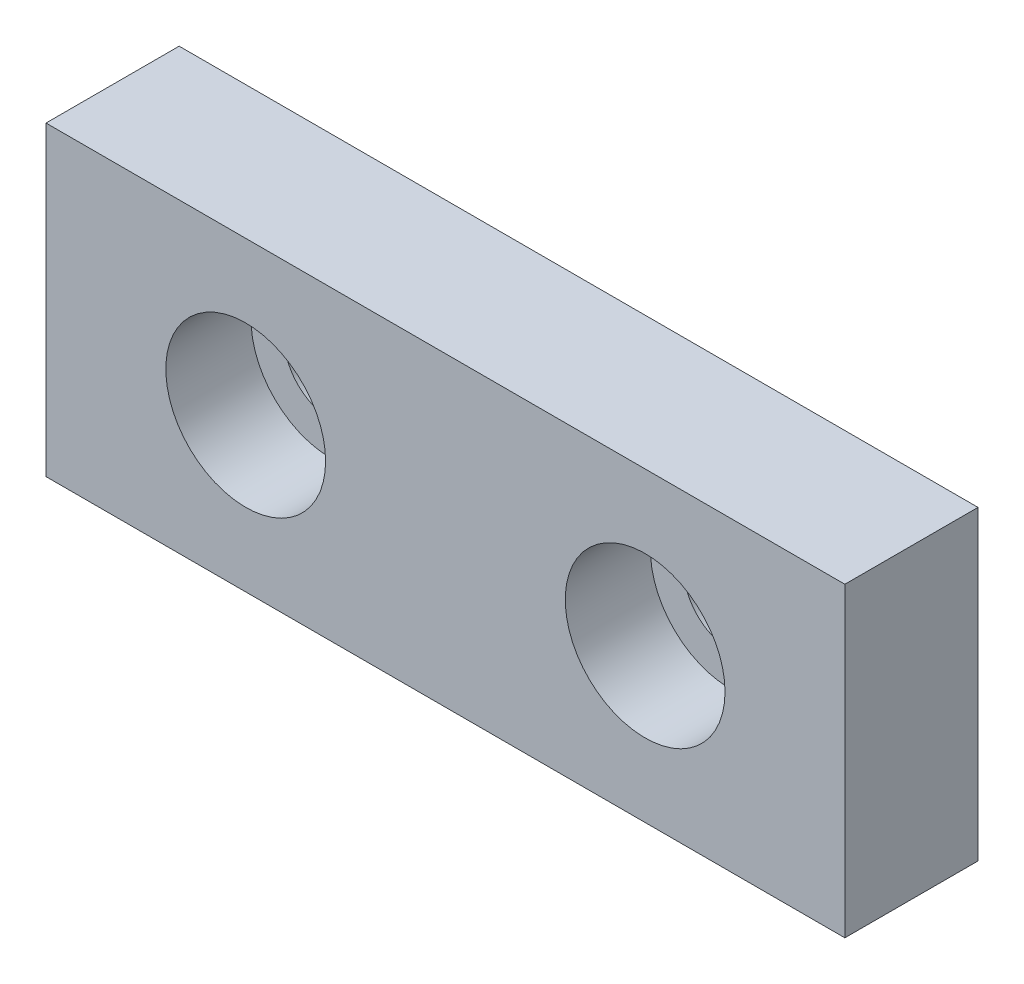
SolidWorks part; units mm, degrees
ref_plane "Front Plane" through (0, 0, 0) normal (0, 0, 1) x (1, 0, 0)
ref_plane "Top Plane" through (0, 0, 0) normal (0, 1, 0) x (1, 0, 0)
ref_plane "Right Plane" through (0, 0, 0) normal (1, 0, 0) x (0, 0, -1)
sketch "Sketch1" plane through (0, 0, 0) normal (0, 0, 1) x (1, 0, 0)
  line L1 (-15, 5.75) -> (15, 5.75)
  line L2 (-15, 5.75) -> (-15, -5.75)
  line L3 (-15, -5.75) -> (15, -5.75)
  line L4 (15, 5.75) -> (15, -5.75)
  line L5 (-15, 5.75) -> (15, -5.75) construction
  line L6 (-15, -5.75) -> (15, 5.75) construction
  point P0 (0, 0)
  dimension "D1" = 30
  dimension "D2" = 11.5
extrude "Boss-Extrude1" add sketch "Sketch1" along normal blind 5
sketch "Sketch2" plane through (0, 0, 5) normal (0, 0, 1) x (1, 0, 0)
  line L0 (-15, 5.75) -> (-15, -5.75) construction
  line L1 (15, -5.75) -> (15, 5.75) construction
  circle A0 centre (-7.5, 0) radius 1.75
  circle A1 centre (7.5, 0) radius 1.75
  dimension "D1" = 3.5
  dimension "D3" = 3.5
  dimension "D2" = 7.5
  dimension "D4" = 7.5
extrude "Cut-Extrude1" cut sketch "Sketch2" against normal through all
sketch "Sketch3" plane through (0, 0, 5) normal (0, 0, 1) x (1, 0, 0)
  circle A0 centre (-7.5, 0) radius 3
  circle A1 centre (7.5, 0) radius 3
  dimension "D1" = 6
  dimension "D2" = 6
extrude "Cut-Extrude4" cut sketch "Sketch3" against normal blind 3.2
